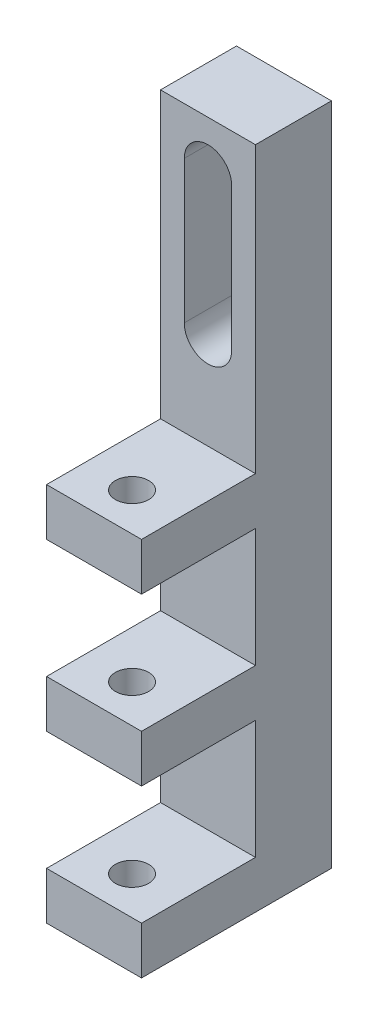
SolidWorks part; units mm, degrees
ref_plane "前视基准面" through (0, 0, 0) normal (0, 0, 1) x (1, 0, 0)
ref_plane "上视基准面" through (0, 0, 0) normal (0, 1, 0) x (1, 0, 0)
ref_plane "右视基准面" through (0, 0, 0) normal (1, 0, 0) x (0, 0, -1)
sketch "草图1" plane through (0, 0, 0) normal (0, 0, 1) x (1, 0, 0)
  line L0 (-14.4944, 5.2247) -> (-14.4944, -14.7753) construction
  line L1 (-14.4944, -14.7753) -> (-4.4944, -14.7753) construction
  line L2 (-4.4944, 5.2247) -> (-4.4944, -34.7753)
  line L3 (-4.4944, -14.7753) -> (5.5056, -14.7753) construction
  line L4 (-4.4944, 5.2247) -> (5.5056, 5.2247)
  line L5 (-4.4944, 5.2247) -> (-4.4944, -34.7753)
  line L6 (-4.4944, -34.7753) -> (5.5056, -34.7753)
  line L7 (5.5056, 5.2247) -> (5.5056, -34.7753)
  line L8 (-4.4944, 5.2247) -> (5.5056, 5.2247)
  line L9 (-4.4944, 5.2247) -> (-4.4944, 0.2247)
  line L10 (-4.4944, 0.2247) -> (5.5056, 0.2247)
  line L11 (5.5056, 5.2247) -> (5.5056, 0.2247)
  line L12 (-4.4944, -34.7753) -> (5.5056, -34.7753)
  line L13 (-4.4944, -34.7753) -> (-4.4944, -29.7753)
  line L14 (-4.4944, -29.7753) -> (5.5056, -29.7753)
  line L15 (5.5056, -34.7753) -> (5.5056, -29.7753)
  line L16 (-4.4944, 25.2247) -> (5.5056, 5.2247) construction
  line L17 (-4.4944, -12.2753) -> (5.5056, -12.2753)
  line L18 (-4.4944, -12.2753) -> (-4.4944, -17.2753)
  line L19 (-4.4944, -17.2753) -> (5.5056, -17.2753)
  line L20 (5.5056, -12.2753) -> (5.5056, -17.2753)
  line L21 (-4.4944, -12.2753) -> (5.5056, -17.2753) construction
  line L22 (-4.4944, -17.2753) -> (5.5056, -12.2753) construction
  line L23 (-4.4944, 5.2247) -> (5.5056, 5.2247)
  line L24 (-4.4944, 5.2247) -> (-4.4944, 25.2247)
  line L25 (-4.4944, 25.2247) -> (5.5056, 25.2247)
  line L26 (5.5056, 5.2247) -> (5.5056, 25.2247)
  circle A0 centre (0.5056, 15.2247) radius 2.5
  point P6 (-4.4944, -14.7753)
  point P12 (0.5056, -14.7753)
  dimension "D1" = 20
  dimension "D2" = 10
  dimension "D3" = 40
  dimension "D4" = 10
  dimension "D5" = 5
  dimension "D6" = 5
  dimension "D7" = 5
  dimension "D8" = 20
extrude "凸台-拉伸1" add sketch "草图1" along normal blind 5 contours L4 L26 L25 L24 A0 | L5 L17 L7 L10 | L19 L5 L14 L7 region at (-4.2708, 15.2247, 0) region at (0.5056, -6.0253, 0) region at (0.5056, -23.5253, 0)
extrude "凸台-拉伸2" add sketch "草图1<3>" along normal blind 17 contours L2 L10 L7 L4 | L2 L19 L7 L17 | L14 L2 L6 L7 region at (0.5056, 2.7247, 0) region at (0.5056, -14.7753, 0) region at (0.5056, -32.2753, 0)
sketch "草图1<3>" plane through (0, 0, 0) normal (0, 0, 1) x (1, 0, 0) same geometry as "草图1"
sketch "草图2" plane through (0, 5.2247, 0) normal (0, 1, 0) x (1, 0, 0)
  line L0 (-4.4944, -17) -> (5.5056, -17) construction
  line L1 (0.5056, -17) -> (0.5056, -13) construction
  circle A0 centre (0.5056, -13) radius 1.75
  dimension "D1" = 4
extrude "切除-拉伸1" cut sketch "草图2" against normal blind 49
sketch "草图3" plane through (5.5056, 0, 0) normal (1, 0, 0) x (0, 0, -1)
  line L1 (0, 25.2247) -> (3, 25.2247)
  line L2 (0, 25.2247) -> (0, -34.7753)
  line L3 (0, -34.7753) -> (3, -34.7753)
  line L4 (3, 25.2247) -> (3, -34.7753)
  dimension "D1" = 60
  dimension "D2" = 3
extrude "凸台-拉伸3" add sketch "草图3" against normal blind 10
sketch "草图4" plane through (0, 0, 5) normal (0, 0, 1) x (1, 0, 0)
  line L0 (-4.4944, 5.2247) -> (-4.4944, 25.2247) construction
  line L1 (-4.4944, 25.2247) -> (5.5056, 25.2247)
  line L2 (-4.4944, 25.2247) -> (-4.4944, 35.2247)
  line L3 (-4.4944, 35.2247) -> (5.5056, 35.2247)
  line L4 (5.5056, 25.2247) -> (5.5056, 35.2247)
  line L5 (-4.4944, 35.2247) -> (5.5056, 25.2247) construction
  line L6 (0.5056, 17.7247) -> (0.5056, 12.7247) construction
  circle A0 centre (0.5056, 30.2247) radius 2.5
  circle A1 centre (0.5056, 15.2247) radius 2.5 construction
  circle A2 centre (0.5056, 15.2247) radius 2.5 construction
  point P15 (1.5298, 12.3704)
  point P16 (0, 0)
  dimension "D1" = 10
  dimension "D2" = 10
extrude "凸台-拉伸4" add sketch "草图4" against normal blind 8
sketch "草图6" plane through (0, 0, 5) normal (0, 0, 1) x (1, 0, 0)
  line L0 (3.0056, 30.2247) -> (-1.9944, 30.2247) construction
  line L1 (-1.9944, 15.2247) -> (3.0056, 15.2247) construction
  line L2 (-1.9944, 30.2247) -> (-1.9944, 15.2247)
  line L3 (3.0056, 30.2247) -> (3.0056, 15.2247)
  circle A0 centre (0.5056, 30.2247) radius 2.5 construction
  circle A1 centre (0.5056, 30.2247) radius 2.5
  circle A2 centre (0.5056, 15.2247) radius 2.5 construction
  circle A3 centre (0.5056, 15.2247) radius 2.5
  circle M1 centre (0.5056, 15.2247) radius 2.5
  circle M6 centre (0.5056, 30.2247) radius 2.5
extrude "切除-拉伸2" cut sketch "草图6" against normal blind 8 contours M6 | L3 L2 M6 M1 | M1 region at (0.5056, 22.7247, 5) region at (0.5056, 30.2247, 5) region at (0.5056, 15.2247, 5)
